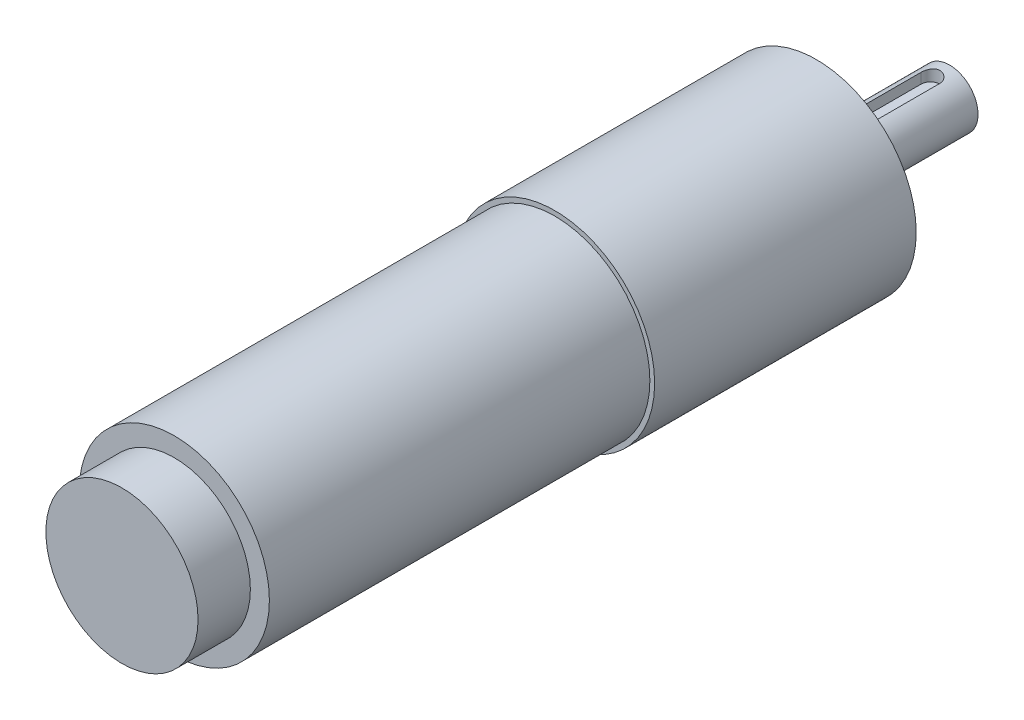
SolidWorks part; units mm, degrees
ref_plane "前视基准面" through (0, 0, 0) normal (0, 0, 1) x (1, 0, 0)
ref_plane "上视基准面" through (0, 0, 0) normal (0, 1, 0) x (1, 0, 0)
ref_plane "右视基准面" through (0, 0, 0) normal (1, 0, 0) x (0, 0, -1)
other "re40"
sketch "草图1" plane through (0, 0, 0) normal (0, 0, 1) x (1, 0, 0)
  circle A0 centre (0, 0) radius 21
  dimension "D1" = 42
extrude "齿轮箱" add sketch "草图1" along normal blind 55
sketch "草图2" plane through (0, 0, 55) normal (0, 0, 1) x (1, 0, 0)
  circle A0 centre (0, 0) radius 20
  dimension "D1" = 40
extrude "电机" add sketch "草图2" along normal blind 80
sketch "草图3" plane through (0, 0, 135) normal (0, 0, 1) x (1, 0, 0)
  line L1 (-15.4942, 0) -> (15.4942, 0) construction
  circle A0 centre (0, 0) radius 16
  dimension "D1" = 32
extrude "编码盘" add sketch "草图3" along normal blind 11
sketch "草图5" plane through (0, 0, 0) normal (0, 0, -1) x (-1, 0, 0)
  circle A0 centre (0, 0) radius 14
  dimension "D1" = 28
extrude "轴承" add sketch "草图5" along normal blind 3
sketch "草图4" plane through (0, 0, -3) normal (0, 0, -1) x (-1, 0, 0)
  circle A0 centre (0, 0) radius 6
  dimension "D1" = 12
extrude "轴" add sketch "草图4" along normal blind 25 separate body
ref_plane "基准面1" through (0, 6, 0) normal (0, 1, 0) x (-1, 0, 0)
sketch "草图6" plane through (0, 6, 0) normal (0, 1, 0) x (-1, 0, 0)
  line L0 (0, 0) -> (0, -29.9259) construction
  line L1 (0, -24) -> (0, -8) construction
  line L2 (-2, -24) -> (-2, -8)
  line L3 (2, -24) -> (2, -8)
  line L4 (-6, -28) -> (6, -28) construction
  arc A0 (-2, -24) -> (2, -24) centre (0, -24) ccw
  arc A1 (2, -8) -> (-2, -8) centre (0, -8) ccw
  point P5 (0, -16)
  dimension "D1" = 4
  dimension "D3" = 16
  dimension "D2" = 4
extrude "切除-拉伸1" cut sketch "草图6" against normal blind 2.5
hole_wizard "M4 螺纹孔1" positions "草图8" profile "草图7" tap size "M4" standard "GB"
sketch "草图8" plane through (0, 0, 0) normal (0, 0, -1) x (-1, 0, 0)
  circle A0 centre (0, 0) radius 17.5 construction
  point P0 (0, 17.5)
  point P10 (17.5, 0)
  point P11 (0, -17.5)
  point P12 (-17.5, 0)
  dimension "D1" = 35
  dimension "D2" = 4
sketch "草图7" plane through (0, 17.5, 0) normal (1, 0, 0) x (0, 1, 0)
  line L0 (0, 0) -> (0, 5.9914)
  line L1 (0, 5.9914) -> (1.65, 5)
  line L2 (1.65, 5) -> (1.65, 0)
  line L5 (1.65, 0) -> (0, 0)
  line L10 (0, 5.9914) -> (-1.65, 5) construction
  line L11 (0, -6.35) -> (0, 107.95) construction
  dimension "螺纹孔钻头直径" = 3.3
  dimension "螺纹孔钻头深度" = 5
  dimension "导头角度" = 118
cosmetic thread "孔螺蚊线1" parameters "D1"=5, "D2"=4
cosmetic thread "孔螺蚊线2" parameters "D1"=5, "D2"=4
cosmetic thread "孔螺蚊线3" parameters "D1"=5, "D2"=4
cosmetic thread "孔螺蚊线4" parameters "D1"=5, "D2"=4
